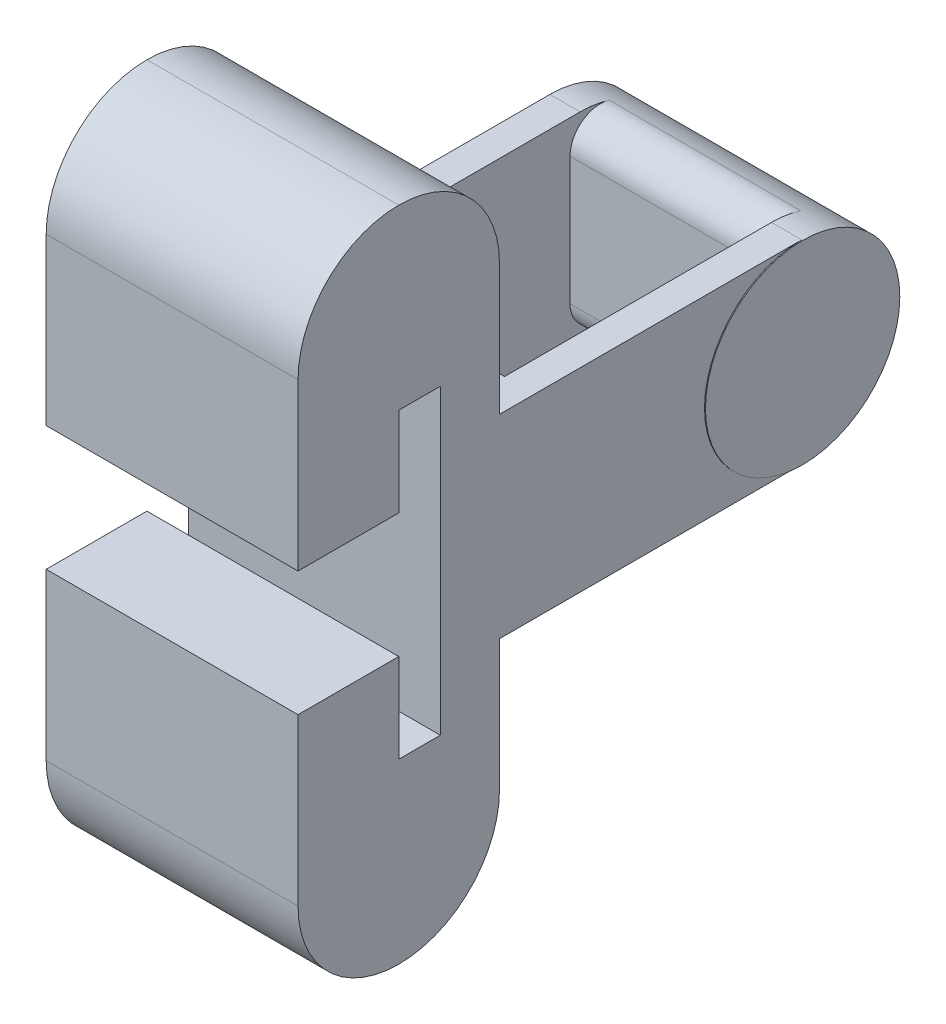
SolidWorks part; units mm, degrees
material "ASTM A36 Steel"
ref_plane "Front Plane" through (0, 0, 0) normal (1, 0, 0) x (0, 1, 0)
ref_plane "Top Plane" through (0, 0, 0) normal (0, 0, 1) x (0, 1, 0)
ref_plane "Right Plane" through (0, 0, 0) normal (0, 1, 0) x (-1, 0, 0)
sketch "Sketch1" plane through (0, 0, 0) normal (1, 0, 0) x (0, 1, 0)
  circle A0 centre (0, 0) radius 24.5059
  dimension "D1" = 24.5059
extrude "Boss-Extrude1" add sketch "Sketch1" along normal blind 0.2286
sketch "Sketch2" plane through (0, 0, 0) normal (-1, 0, 0) x (0, -1, 0)
  line L0 (55, 0) -> (-55, 0) construction
  line L1 (-24.5059, 0) -> (-24.5059, 76.2)
  line L2 (-24.5059, 76.2) -> (24.5059, 76.2)
  line L3 (24.5059, 76.2) -> (24.5059, 0)
  arc A0 (-24.5059, 0) -> (24.5059, 0) centre (0, 0) ccw
  circle A1 centre (0, 0) radius 24.5059 construction
  dimension "D2" = 76.2
extrude "Boss-Extrude2" add sketch "Sketch2" along normal blind 63.5
sketch "Sketch4" plane through (0, 0, 76.2) normal (0, 0, 1) x (1, 0, 0)
  line L0 (-31.75, 24.5059) -> (-31.75, -24.5059) construction
  line L1 (-63.5, 24.5059) -> (0, 24.5059) construction
  line L2 (-63.5, -24.5059) -> (0, -24.5059) construction
  line L4 (0, -55) -> (0, 55) construction
  line L5 (-63.5, 38.1) -> (-63.5, -38.1)
  line L6 (-63.5, -38.1) -> (0, -38.1)
  line L7 (0, -38.1) -> (0, 38.1)
  line L8 (0, 38.1) -> (-63.5, 38.1)
  line L9 (55, 0) -> (-55, 0) construction
  dimension "D1" = 31.75
  dimension "D2" = 31.75
  dimension "D3" = 38.1
  dimension "D4" = 63.5
  dimension "D5" = 76.2
extrude "Boss-Extrude4" add sketch "Sketch4" along normal blind 14.9298
sketch3d "3DSketch1"
  point P0 (-33.4324, 15.0066, 91.1298)
sketch3d "3DSketch2"
  point P0 (-32.8005, -21.279, 91.1298)
sketch "Sketch5" plane through (0, 38.1, 0) normal (0, 1, 0) x (-1, 0, 0)
  line L0 (0, 76.2) -> (63.5, 76.2)
  line L1 (63.5, 76.2) -> (63.5, 127)
  line L2 (63.5, 127) -> (0, 127)
  line L3 (0, 127) -> (0, 76.2)
  dimension "D1" = 50.8
extrude "Boss-Extrude5" add sketch "Sketch5" along normal blind 44.7893
fillet "Fillet2" radius 25.4 2 edges at (-31.75, 82.8893, 76.2) (-31.75, 82.8893, 127)
sketch "Sketch7" plane through (0, 38.1, 0) normal (0, -1, 0) x (1, 0, 0)
  line L0 (-63.5, 127) -> (0, 127)
  line L1 (0, 127) -> (0, 101.6)
  line L2 (0, 127) -> (0, 91.1298) construction
  line L3 (0, 101.6) -> (-63.5, 101.6)
  line L4 (-63.5, 91.1298) -> (-63.5, 127) construction
  line L5 (-63.5, 101.6) -> (-63.5, 127)
  dimension "D2" = 63.5
extrude "Boss-Extrude7" add sketch "Sketch7" along normal blind 22.418
mirror "Mirror1" about plane through (0, 0, 0) normal (0, 1, 0) of "Fillet2", "Boss-Extrude7", "Boss-Extrude5"
sketch "Sketch10" plane through (0, 24.5059, 0) normal (0, 1, 0) x (-1, 0, 0)
  line L0 (0, 2.54) -> (31.6432, 2.54) construction
  line L1 (0, 76.2) -> (0, 0) construction
  line L2 (7.62, 2.54) -> (55.88, 2.54)
  line L3 (55.88, 2.54) -> (55.88, 67.31)
  line L4 (55.88, 67.31) -> (7.62, 67.31)
  line L5 (7.62, 67.31) -> (7.62, 2.54)
  line L6 (63.5, 76.2) -> (63.5, 0) construction
  line L7 (63.5, 0) -> (0, 0) construction
  line L8 (63.5, 76.2) -> (0, 76.2) construction
  dimension "D1" = 7.62
  dimension "D2" = 7.62
  dimension "D3" = 2.54
  dimension "D4" = 8.89
extrude "Cut-Extrude2" cut sketch "Sketch10" against normal through all
fillet "Fillet3" radius 7.62 2 edges at (-31.75, -24.5059, 2.54) (-31.75, 24.5059, 2.54)
equation "\"force\"= 800"
equation "\"safetyfactor\"= 4"
equation "\"yieldstrength\"= 3629.43442"
equation "\"E\"= 29007547.43"
equation "\"lengthA\"=0.8"
equation "\"moduliz\"= ( \"safetyfactor\" * \"lengthA\" * ( \"force\" * 2 ) ) / ( 2 * \"yieldstrength\" )"
equation "\"ra\"= ( 4 * \"moduliz\" / pi ) ^ ( 1 / 3 )"
equation "\"barea\"= ( \"force\" * \"safetyfactor\" ) / ( \"yieldstrength\" )"
equation "\"bthick\"= \"barea\" / \"wb\""
equation "\"wb\"= 1"
equation "\"lc\"= 3"
equation "\"carea\"= ( ( \"force\" * 2 ) * \"safetyfactor\" ) / \"yieldstrength\""
equation "\"hc\"= \"carea\" / \"lc\""
equation "\"hd\"= 0.5"
equation "\"darea\"= ( \"force\" * \"safetyfactor\" ) / \"yieldstrength\""
equation "\"ld\"= \"darea\" / \"hd\""
equation "\"le\"=1"
equation "\"earea\"= ( 2 * \"force\" * \"safetyfactor\" ) / \"yieldstrength\""
equation "\"he\"= \"earea\" / \"le\""
equation "\"D1@Sketch1\"=\"ra\""
equation "\"D1@Boss-Extrude2\"=2.50"
equation "\"D4@Sketch4\"=2.5"
equation "\"D5@Sketch4\"=\"lc\""
equation "\"D1@Boss-Extrude4\"=\"hc\""
equation "\"D1@Boss-Extrude5\"=\"ld\""
equation "\"D1@Sketch7\"=\"le\""
equation "\"D1@Boss-Extrude1\"=0.009in"
